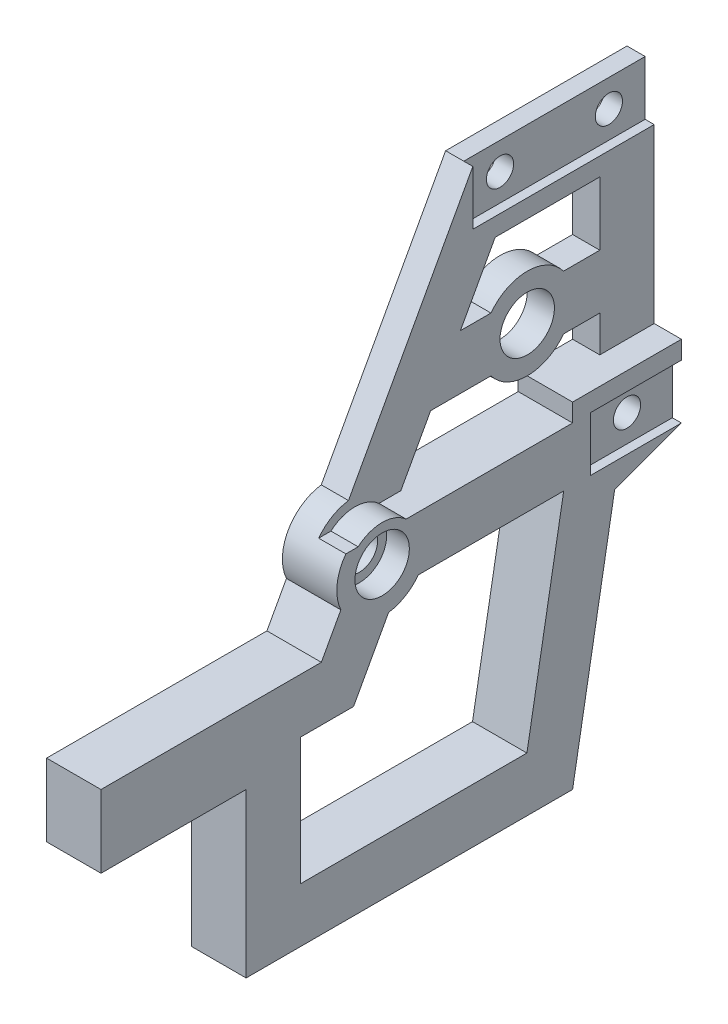
SolidWorks part; units mm, degrees
material "1060 Alloy"
ref_plane "Front Plane" through (0, 0, 0) normal (0, 0, 1) x (1, 0, 0)
ref_plane "Top Plane" through (0, 0, 0) normal (0, 1, 0) x (1, 0, 0)
ref_plane "Right Plane" through (0, 0, 0) normal (1, 0, 0) x (0, 0, -1)
sketch "Sketch1" plane through (0, 0, 0) normal (1, 0, 0) x (0, 0, -1)
  line L0 (52, 0) -> (56.6412, 26.3216)
  line L1 (16, 0) -> (52, 0)
  line L2 (0, 18) -> (0, 26)
  line L3 (44, 62) -> (64, 62)
  line L4 (64, 29) -> (64, 62)
  line L5 (56.6412, 26.3216) -> (64, 29)
  line L6 (16, 0) -> (16, 18)
  line L7 (16, 18) -> (0, 18)
  line L8 (0, 26) -> (24.296, 26)
  line L9 (44, 62) -> (30.2889, 36.9492)
  line L10 (44, 62) -> (44, 56) construction
  line L11 (44, 56) -> (64, 56) construction
  line L12 (64, 29) -> (54, 29) construction
  line L13 (54, 29) -> (54, 35) construction
  line L14 (54, 35) -> (64, 35) construction
  line L15 (31, 32) -> (44, 55.7516) construction
  line L16 (39.346, 41) -> (36.062, 35)
  line L17 (31, 32) -> (59, 32) construction
  line L18 (50, 44) -> (64, 44) construction
  line L19 (39.346, 41) -> (46, 41)
  line L20 (46.4613, 54) -> (42.6299, 47)
  line L21 (42.6299, 47) -> (46, 47)
  line L22 (54, 47) -> (58, 47)
  line L23 (58, 47) -> (58, 54)
  line L24 (58, 54) -> (46.4613, 54)
  line L25 (54, 41) -> (58, 41)
  line L26 (58, 41) -> (58, 37)
  line L27 (58, 37) -> (52, 37)
  line L28 (52, 37) -> (52, 35)
  line L29 (52, 35) -> (36.062, 35)
  line L30 (35, 29) -> (51.0209, 29)
  line L31 (27.852, 20) -> (31.7111, 27.0508)
  line L32 (51.0209, 29) -> (46.9654, 6)
  line L33 (46.9654, 6) -> (22, 6)
  line L34 (22, 6) -> (22, 20)
  line L35 (22, 20) -> (27.852, 20)
  line L36 (26.4479, 29.9316) -> (24.296, 26)
  circle A0 centre (59, 32) radius 1.5
  circle A1 centre (50, 44) radius 3
  circle A2 centre (60, 59) radius 1.5
  circle A3 centre (48, 59) radius 1.5
  circle A4 centre (31, 32) radius 2
  circle A5 centre (31, 32) radius 5 construction
  arc A6 (46, 47) -> (54, 47) centre (50, 44) cw
  arc A7 (46, 41) -> (54, 41) centre (50, 44) ccw
  arc A8 (31.7111, 27.0508) -> (35, 29) centre (31, 32) ccw
  arc A9 (30.2889, 36.9492) -> (26.4479, 29.9316) centre (31, 32) ccw
  dimension "D1" = 6
  dimension "D2" = 16
  dimension "D4" = 3
  dimension "D14" = 4
  dimension "D24" = 10
  dimension "D27" = 5
  dimension "D3" = 18
  dimension "D5" = 44
  dimension "D6" = 50
  dimension "D7" = 64
  dimension "D8" = 62
  dimension "D9" = 4
  dimension "D10" = 12
  dimension "D11" = 3
  dimension "D12" = 3
  dimension "D13" = 5
  dimension "D15" = 8
  dimension "D16" = 32
  dimension "D17" = 31
  dimension "D18" = 32
  dimension "D19" = 6
  dimension "D20" = 20
  dimension "D21" = 10
  dimension "D22" = 6
  dimension "D23" = 52
  dimension "D25" = 6
  dimension "D26" = 3
  dimension "D28" = 6
  dimension "D29" = 3
  dimension "D30" = 6
  dimension "D31" = 6
  dimension "D32" = 3
  dimension "D33" = 2
  dimension "D34" = 2
  dimension "D35" = 2
  dimension "D36" = 6
  dimension "D37" = 6
  dimension "D38" = 20
  dimension "D39" = 100
  dimension "D40" = 6
  dimension "D41" = 6
extrude "Boss-Extrude1" add sketch "Sketch1" along normal blind 6
hole_wizard "Tap Drill for M3 Tap1" positions "Sketch5" profile "Sketch4" hole size "M3" standard "ISO"
sketch "Sketch5" plane through (0, 0, 0) normal (0, -1, 0) x (-1, 0, 0)
  line L0 (0, 16) -> (0, 52) construction
  line L2 (-6, 52) -> (0, 52) construction
  line L4 (-6, 16) -> (0, 16) construction
  point P0 (-3, 49)
  point P2 (-3, 19)
  dimension "D1" = 3
  dimension "D2" = 3
  dimension "D3" = 3
sketch "Sketch4" plane through (3, 0, -49) normal (1, 0, 0) x (0, 0, -1)
  line L0 (0, 0) -> (0, 9.7511)
  line L1 (0, 9.7511) -> (1.25, 9)
  line L2 (1.25, 9) -> (1.25, 0)
  line L5 (1.25, 0) -> (0, 0)
  line L10 (0, 9.7511) -> (-1.25, 9) construction
  line L11 (0, -6.35) -> (0, 107.95) construction
  dimension "Hole Dia." = 2.5
  dimension "Hole Depth" = 9
  dimension "Drill Angle" = 118
sketch "Sketch13" plane through (6, 0, 0) normal (1, 0, 0) x (0, 0, -1)
  line L0 (64, 29) -> (64, 62) construction
  line L1 (52, 37) -> (64, 37)
  line L2 (64, 62) -> (44, 62) construction
  line L3 (64, 62) -> (44, 62)
  line L4 (64, 37) -> (64, 62)
  line L5 (30.2889, 36.9492) -> (27, 36.9492)
  line L6 (33.6458, 35) -> (52, 35)
  line L7 (36.062, 35) -> (52, 35) construction
  line L8 (52, 35) -> (52, 37)
  line L9 (52, 35) -> (52, 37) construction
  line L10 (27, 36.9492) -> (27, 35)
  line L11 (44, 62) -> (30.2889, 36.9492)
  line L12 (27, 35) -> (28.3542, 35)
  line L13 (44, 62) -> (30.2889, 36.9492) construction
  arc A1 (28.3542, 35) -> (33.6458, 35) centre (31, 32) cw
  arc A2 (30.2889, 36.9492) -> (26.4479, 29.9316) centre (31, 32) ccw construction
  dimension "D1" = 4
  dimension "D3" = 25
extrude "Cut-Extrude4" cut sketch "Sketch13" against normal blind 3
sketch "Sketch14" plane through (3, 0, 0) normal (1, 0, 0) x (0, 0, -1)
  line L1 (64, 62) -> (44, 62)
  line L2 (64, 62) -> (64, 56)
  line L3 (64, 56) -> (44, 56)
  line L4 (44, 62) -> (44, 56)
  dimension "D1" = 6
extrude "Cut-Extrude5" cut sketch "Sketch14" against normal blind 1
sketch "Sketch15" plane through (6, 0, 0) normal (1, 0, 0) x (0, 0, -1)
  line L1 (64, 29) -> (54, 29)
  line L2 (64, 29) -> (64, 35)
  line L3 (64, 35) -> (54, 35)
  line L4 (54, 29) -> (54, 35)
  dimension "D1" = 10
  dimension "D2" = 6
extrude "Cut-Extrude6" cut sketch "Sketch15" against normal blind 1
sketch "Sketch16" plane through (6, 0, 0) normal (1, 0, 0) x (0, 0, -1)
  circle A0 centre (31, 32) radius 3
  dimension "D1" = 6
extrude "Cut-Extrude7" cut sketch "Sketch16" against normal blind 2.5
